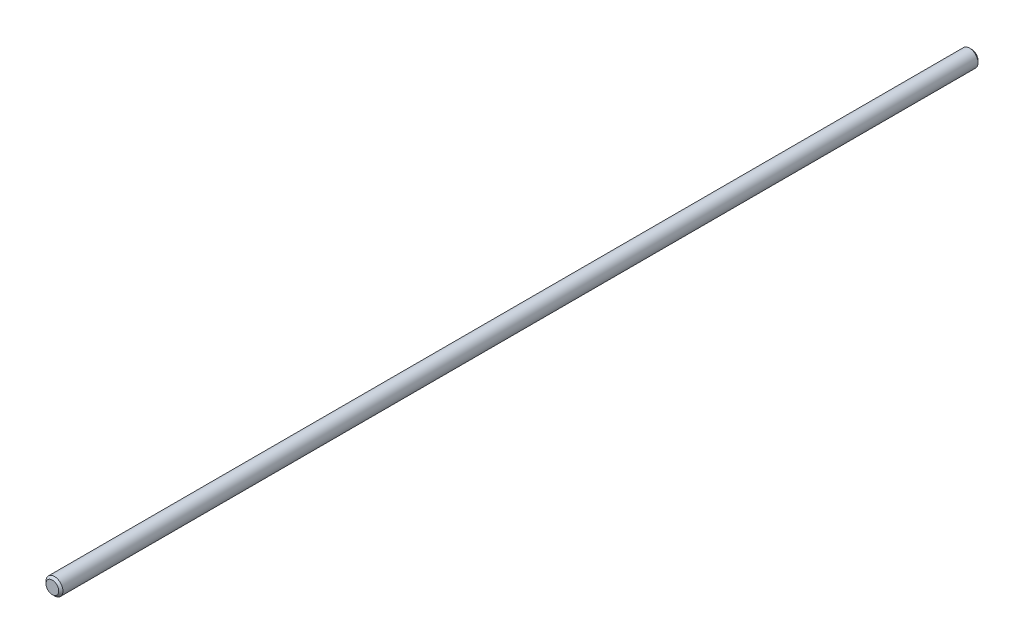
SolidWorks part; units mm, degrees
ref_plane "Piano frontale" through (0, 0, 0) normal (0, 0, 1) x (1, 0, 0)
ref_plane "Piano superiore" through (0, 0, 0) normal (0, 1, 0) x (1, 0, 0)
ref_plane "Piano destro" through (0, 0, 0) normal (1, 0, 0) x (0, 0, -1)
sketch "Schizzo1" plane through (0, 0, 0) normal (0, 0, 1) x (1, 0, 0)
  circle A0 centre (0, 0) radius 4
  dimension "D1" = 8
extrude "Estrusione-Estrusione1" add sketch "Schizzo1" along normal blind 435
chamfer "Smusso1" distance 1 angle 45 2 edges at (4, 0, 0) (4, 0, 435)
sketch "Schizzo2" plane through (0, 0, 0) normal (0, 1, 0) x (1, 0, 0)
  line L0 (4, -1) -> (4, -434) construction
